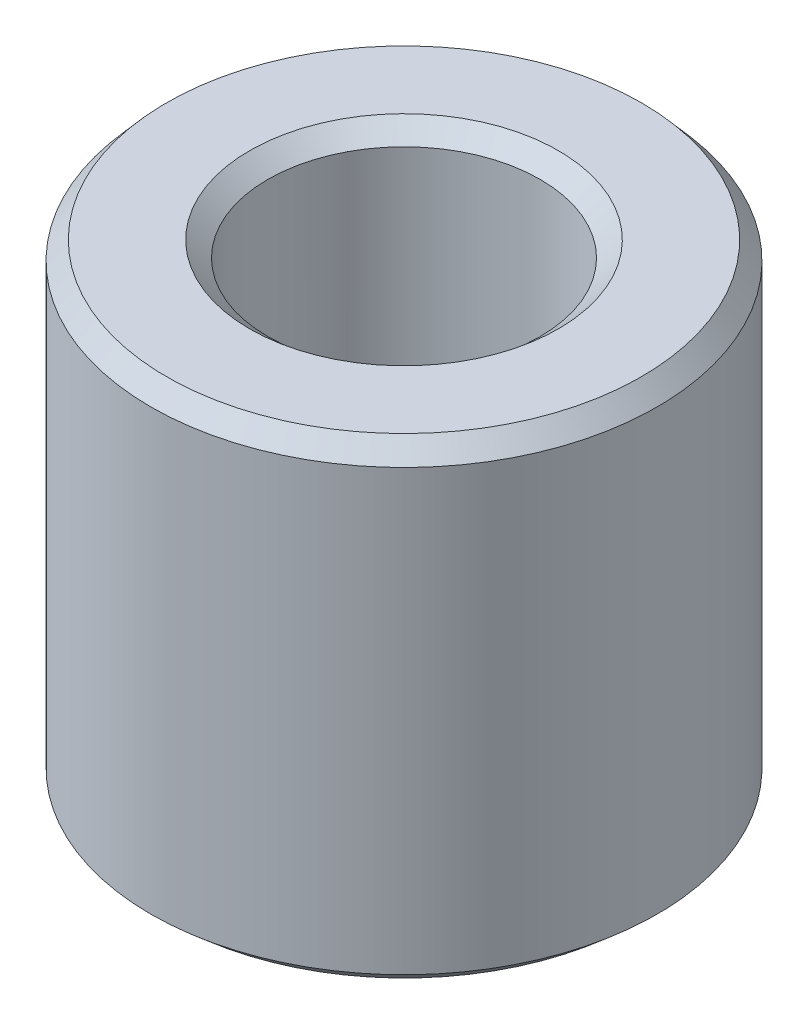
SolidWorks part; units mm, degrees
ref_plane "Front Plane" through (0, 0, 0) normal (0, 0, 1) x (1, 0, 0)
ref_plane "Top Plane" through (0, 0, 0) normal (0, 1, 0) x (1, 0, 0)
ref_plane "Right Plane" through (0, 0, 0) normal (1, 0, 0) x (0, 0, -1)
sketch "Sketch1" plane through (0, 0, 0) normal (0, 1, 0) x (1, 0, 0)
  circle A0 centre (0, 0) radius 52.5
  dimension "SLEEVE_OD" = 105
extrude "Boss-Extrude1" add sketch "Sketch1" along normal blind 98.1657
sketch "Sketch2" plane through (0, 0, 0) normal (0, 1, 0) x (1, 0, 0)
  circle A0 centre (0, 0) radius 28.2359
  dimension "BORE_D" = 56.4718
extrude "Cut-Extrude1" cut sketch "Sketch2" along normal through all
chamfer "Chamfer1" distance 3.7847 angle 40.817 4 edges at (0, 98.1657, 28.2359) (0, 0, 28.2359) (0, 0, 52.5) (0, 98.1657, 52.5) first distance on face at (0, 98.1657, 28.2359) first distance on face at (0, 0, 28.2359) first distance on face at (0, 98.1657, 52.5)
